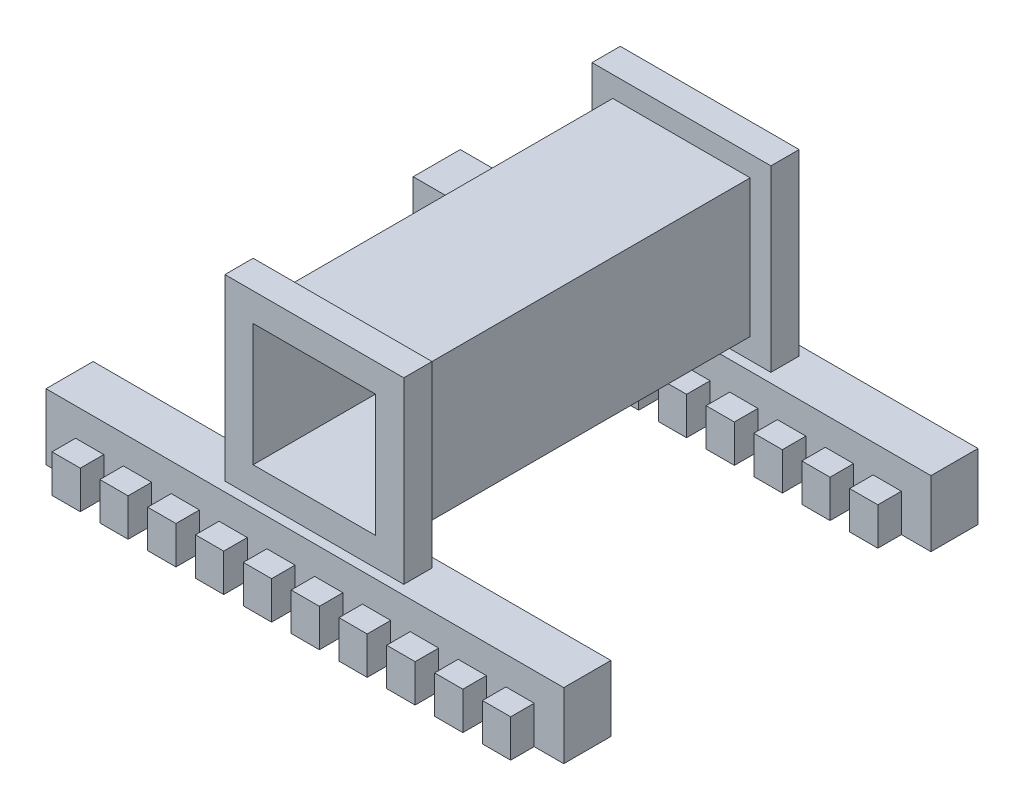
SolidWorks part; units mm, degrees
ref_plane "前视基准面" through (0, 0, 0) normal (0, 0, 1) x (1, 0, 0)
ref_plane "上视基准面" through (0, 0, 0) normal (0, 1, 0) x (1, 0, 0)
ref_plane "右视基准面" through (0, 0, 0) normal (1, 0, 0) x (0, 0, -1)
sketch "草图1" plane through (0, 0, 0) normal (0, 0, 1) x (1, 0, 0)
  line L0 (-9.5, 9.5) -> (9.5, 9.5)
  line L1 (-6.5, -6.5) -> (6.5, -6.5)
  line L2 (-6.5, -6.5) -> (-6.5, 6.5)
  line L3 (-6.5, 6.5) -> (6.5, 6.5)
  line L4 (6.5, -6.5) -> (6.5, 6.5)
  line L5 (-6.5, -6.5) -> (6.5, 6.5) construction
  line L6 (-6.5, 6.5) -> (6.5, -6.5) construction
  line L7 (9.5, -9.5) -> (9.5, 9.5)
  line L8 (-9.5, -9.5) -> (9.5, -9.5)
  line L9 (-9.5, -9.5) -> (-9.5, 9.5)
  line L10 (-7.3, 7.3) -> (7.3, 7.3)
  line L11 (7.3, -7.3) -> (7.3, 7.3)
  line L12 (-7.3, -7.3) -> (7.3, -7.3)
  line L13 (-7.3, -7.3) -> (-7.3, 7.3)
  line L15 (-27.5, -9.5) -> (27.5, -9.5)
  line L16 (-27.5, -9.5) -> (-27.5, -16.5)
  line L17 (-27.5, -16.5) -> (27.5, -16.5)
  line L18 (27.5, -9.5) -> (27.5, -16.5)
  point P0 (0, 0)
  dimension "D1" = 3
  dimension "D2" = 0.8
extrude "凸台-拉伸1" add sketch "草图1" along normal mid plane 42 contours L18 L15 L8 L16 L17 | L9 L8 L7 L0 L12 L13 L10 L11 | L13 L10 L11 L12 region at (0, 9.2313, 0) region at (0, -13, 0)
extrude "切除-拉伸1" cut sketch "草图1<3>" against normal mid plane 42 contours L2 L3 L4 L1
sketch "草图1<3>" plane through (0, 0, 0) normal (0, 0, 1) x (1, 0, 0) same geometry as "草图1"
sketch "草图2" plane through (0, 0, 0) normal (1, 0, 0) x (0, 0, -1)
  line L0 (21, -16.5) -> (21, -9.5) construction
  line L1 (21, -9.5) -> (-21, -9.5) construction
  line L2 (-21, -9.5) -> (-21, -16.5) construction
  line L3 (-21, -16.5) -> (21, -16.5) construction
  line L4 (21, -9.5) -> (21, 9.5) construction
  line L5 (21, 9.5) -> (-21, 9.5) construction
  line L6 (-21, 9.5) -> (-21, -9.5) construction
  line L7 (-21, -9.5) -> (21, -9.5) construction
  line L8 (21, -16.5) -> (21, -9.5)
  line L9 (21, -9.5) -> (-21, -9.5)
  line L10 (-21, -9.5) -> (-21, -16.5)
  line L11 (-21, -16.5) -> (21, -16.5)
  line L12 (21, -9.5) -> (21, 9.5)
  line L13 (21, 9.5) -> (-21, 9.5)
  line L14 (-21, 9.5) -> (-21, -9.5)
  line L15 (-21, -9.5) -> (21, -9.5)
extrude "切除-拉伸6" cut sketch "草图1<12>" against normal mid plane 36 contours L1 L4 L3 L2 | L9 L0 L7 L8 | L13 L10 L11 L12 region at (0, 0, 0)
sketch "草图1<12>" plane through (0, 0, 0) normal (0, 0, 1) x (1, 0, 0) same geometry as "草图1"
extrude "切除-拉伸7" cut sketch "草图1<13>" against normal mid plane 29 contours L18 L15 L8 L16 L17 region at (0, -13, 0)
sketch "草图1<13>" plane through (0, 0, 0) normal (0, 0, 1) x (1, 0, 0) same geometry as "草图1"
sketch "草图4" plane through (0, 0, 0) normal (1, 0, 0) x (0, 0, -1)
  line L0 (-21, -9.5) -> (-14.5, -9.5) construction
  line L1 (-14.5, -9.5) -> (-14.5, -16.5) construction
  line L2 (-14.5, -16.5) -> (-21, -16.5) construction
  line L3 (-21, -16.5) -> (-21, -9.5) construction
  line L4 (-18, 9.5) -> (-18, -9.5) construction
  line L5 (-18, -9.5) -> (-21, -9.5) construction
  line L6 (-21, -9.5) -> (-21, 9.5) construction
  line L7 (-21, 9.5) -> (-18, 9.5) construction
  line L8 (-18, -7.3) -> (-18, 7.3) construction
  line L9 (-18, 7.3) -> (18, 7.3) construction
  line L10 (18, 7.3) -> (18, -7.3) construction
  line L11 (18, -7.3) -> (-18, -7.3) construction
  line L12 (21, -9.5) -> (18, -9.5) construction
  line L13 (18, -9.5) -> (18, 9.5) construction
  line L14 (18, 9.5) -> (21, 9.5) construction
  line L15 (21, 9.5) -> (21, -9.5) construction
  line L16 (14.5, -16.5) -> (14.5, -9.5) construction
  line L17 (14.5, -9.5) -> (21, -9.5) construction
  line L18 (21, -9.5) -> (21, -16.5) construction
  line L19 (21, -16.5) -> (14.5, -16.5) construction
  line L20 (-21, -9.5) -> (-14.5, -9.5)
  line L21 (-14.5, -9.5) -> (-14.5, -16.5)
  line L22 (-14.5, -16.5) -> (-21, -16.5)
  line L23 (-21, -16.5) -> (-21, -9.5)
  line L24 (-18, 9.5) -> (-18, -9.5)
  line L25 (-18, -9.5) -> (-21, -9.5)
  line L26 (-21, -9.5) -> (-21, 9.5)
  line L27 (-21, 9.5) -> (-18, 9.5)
  line L28 (-18, -7.3) -> (-18, 7.3)
  line L29 (-18, 7.3) -> (18, 7.3)
  line L30 (18, 7.3) -> (18, -7.3)
  line L31 (18, -7.3) -> (-18, -7.3)
  line L32 (21, -9.5) -> (18, -9.5)
  line L33 (18, -9.5) -> (18, 9.5)
  line L34 (18, 9.5) -> (21, 9.5)
  line L35 (21, 9.5) -> (21, -9.5)
  line L36 (14.5, -16.5) -> (14.5, -9.5)
  line L37 (14.5, -9.5) -> (21, -9.5)
  line L38 (21, -9.5) -> (21, -16.5)
  line L39 (21, -16.5) -> (14.5, -16.5)
  line L40 (21, -9.5) -> (24.5, -9.5)
  line L41 (24.5, -9.5) -> (24.5, -16.5)
  line L42 (24.5, -16.5) -> (21, -16.5)
  line L43 (-21, -16.5) -> (-24.5049, -16.5)
  line L44 (-24.5049, -16.5) -> (-24.5049, -9.5)
  line L45 (-24.5049, -9.5) -> (-21, -9.5)
extrude "凸台-拉伸2" add sketch "草图4" along normal mid plane 55 contours L42 L41 L40 L38 | L45 L44 L43 L23 region at (0, -13, 22.7525) region at (0, -13, -22.75)
sketch "草图5" plane through (0, 0, -24.5) normal (0, 0, -1) x (-1, 0, 0)
  line L3 (-17.78, -12.5036) -> (-17.78, -16.5)
  line L4 (27.5, -16.5) -> (27.5, -9.5)
  line L5 (27.5, -9.5) -> (-27.5, -9.5)
  line L6 (-27.5, -9.5) -> (-27.5, -16.5)
  line L7 (-27.5, -16.5) -> (27.5, -16.5)
  line L8 (27.5, -16.5) -> (27.5, -9.5)
  line L9 (27.5, -9.5) -> (-27.5, -9.5)
  line L10 (-27.5, -9.5) -> (-27.5, -16.5)
  line L12 (-9.5, -9.5) -> (9.5, -9.5)
  line L13 (-9.5, 9.5) -> (-9.5, -9.5)
  line L14 (9.5, 9.5) -> (-9.5, 9.5)
  line L15 (9.5, -9.5) -> (9.5, 9.5)
  line L16 (-9.5, -9.5) -> (9.5, -9.5)
  line L17 (-9.5, 9.5) -> (-9.5, -9.5)
  line L18 (9.5, 9.5) -> (-9.5, 9.5)
  line L19 (9.5, -9.5) -> (9.5, 9.5)
  line L20 (-17.78, -16.5) -> (-12.7, -16.5)
  line L21 (-12.7, -16.5) -> (-12.7, -12.5036)
  line L23 (-7.62, -12.5036) -> (-7.62, -16.5)
  line L24 (-27.5, -16.5) -> (27.5, -16.5) construction
  line L26 (-2.54, -16.5) -> (-2.54, -12.4956)
  line L30 (7.62, -16.5) -> (7.62, -12.5)
  line L32 (12.7, -12.5) -> (12.7, -16.5)
  line L33 (12.7, -16.5) -> (17.78, -16.5)
  line L34 (17.78, -16.5) -> (17.78, -12.487)
  line L36 (22.8593, -12.487) -> (22.8593, -16.5)
  line L37 (22.8593, -16.5) -> (27.5, -16.5)
  line L38 (-27.5, -16.5) -> (-22.86, -16.5)
  line L49 (-12.7, -12.5036) -> (-7.62, -12.5036)
  line L50 (-21.36, -16.5) -> (-24.36, -16.5)
  line L55 (-11.187, -12.5036) -> (-14.213, -12.5036)
  line L56 (-11.187, -12.5036) -> (-11.187, -16.5)
  line L61 (-6.12, -16.5) -> (-9.12, -16.5)
  line L62 (-6.12, -16.5) -> (-6.12, -12.5036)
  line L67 (-7.62, -16.5) -> (-2.54, -16.5)
  line L68 (-1.04, -16.4978) -> (-4.04, -16.4978)
  line L73 (-2.54, -12.4956) -> (2.539, -12.4956)
  line L74 (2.539, -16.5) -> (7.62, -16.5)
  line L79 (7.62, -12.5) -> (12.7, -12.5)
  line L80 (17.78, -12.487) -> (22.8593, -12.487)
  line L86 (9.12, -16.5) -> (6.12, -16.5)
  line L91 (9.12, -16.5) -> (9.12, -12.5)
  line L92 (9.12, -12.5) -> (6.12, -12.5)
  line L97 (6.12, -16.5) -> (6.12, -12.5)
  line L98 (9.12, -16.5) -> (6.12, -12.5) construction
  line L101 (-22.86, -16.5) -> (-22.86, -12.5036)
  line L102 (-22.86, -12.5036) -> (-17.78, -12.5036)
  line L103 (-21.36, -16.5) -> (-21.36, -12.5036)
  line L104 (-21.36, -12.5036) -> (-24.36, -12.5036)
  line L105 (-24.36, -16.5) -> (-24.36, -12.5036)
  line L106 (-21.36, -16.5) -> (-24.36, -12.5036) construction
  line L107 (-21.36, -12.5036) -> (-24.36, -16.5) construction
  line L108 (-19.28, -16.5) -> (-16.28, -16.5)
  line L109 (-19.28, -16.5) -> (-19.28, -12.5036)
  line L110 (-19.28, -12.5036) -> (-16.28, -12.5036)
  line L111 (-16.28, -16.5) -> (-16.28, -12.5036)
  line L112 (-19.28, -16.5) -> (-16.28, -12.5036) construction
  line L113 (-19.28, -12.5036) -> (-16.28, -16.5) construction
  line L114 (-11.187, -16.5) -> (-14.213, -16.5)
  line L115 (-14.213, -12.5036) -> (-14.213, -16.5)
  line L116 (-11.187, -12.5036) -> (-14.213, -16.5) construction
  line L117 (-11.187, -16.5) -> (-14.213, -12.5036) construction
  line L118 (-6.12, -12.5036) -> (-9.12, -12.5036)
  line L119 (-9.12, -16.5) -> (-9.12, -12.5036)
  line L120 (-6.12, -16.5) -> (-9.12, -12.5036) construction
  line L121 (-6.12, -12.5036) -> (-9.12, -16.5) construction
  line L122 (-1.04, -16.4978) -> (-1.04, -12.4978)
  line L123 (-1.04, -12.4978) -> (-4.04, -12.4978)
  line L124 (-4.04, -16.4978) -> (-4.04, -12.4978)
  line L125 (-1.04, -16.4978) -> (-4.04, -12.4978) construction
  line L126 (-1.04, -12.4978) -> (-4.04, -16.4978) construction
  line L127 (2.539, -12.4956) -> (2.539, -16.5)
  line L128 (9.12, -12.5) -> (6.12, -16.5) construction
  line L129 (4.04, -16.5) -> (1.038, -16.5)
  line L130 (4.04, -16.5) -> (4.04, -12.4956)
  line L131 (4.04, -12.4956) -> (1.038, -12.4956)
  line L132 (1.038, -16.5) -> (1.038, -12.4956)
  line L133 (4.04, -16.5) -> (1.038, -12.4956) construction
  line L134 (4.04, -12.4956) -> (1.038, -16.5) construction
  line L135 (14.2014, -16.5) -> (11.1986, -16.5)
  line L136 (14.2014, -16.5) -> (14.2014, -12.5)
  line L137 (14.2014, -12.5) -> (11.1986, -12.5)
  line L138 (11.1986, -16.5) -> (11.1986, -12.5)
  line L139 (14.2014, -16.5) -> (11.1986, -12.5) construction
  line L140 (14.2014, -12.5) -> (11.1986, -16.5) construction
  line L141 (19.28, -16.4935) -> (16.28, -16.4935)
  line L142 (19.28, -16.4935) -> (19.28, -12.4935)
  line L143 (19.28, -12.4935) -> (16.28, -12.4935)
  line L144 (16.28, -16.4935) -> (16.28, -12.4935)
  line L145 (19.28, -16.4935) -> (16.28, -12.4935) construction
  line L146 (19.28, -12.4935) -> (16.28, -16.4935) construction
  line L151 (24.3586, -16.5) -> (21.36, -16.5)
  line L152 (24.3586, -16.5) -> (24.3586, -12.487)
  line L153 (24.3586, -12.487) -> (21.36, -12.487)
  line L154 (21.36, -16.5) -> (21.36, -12.487)
  line L155 (24.3586, -16.5) -> (21.36, -12.487) construction
  line L156 (24.3586, -12.487) -> (21.36, -16.5) construction
  point P6 (-22.86, -14.5018)
  point P33 (-17.78, -14.5018)
  point P35 (-17.78, -14.5018)
  point P39 (-12.7, -14.5018)
  point P40 (-12.7, -14.5018)
  point P45 (-7.62, -14.5018)
  point P50 (-2.54, -14.4978)
  point P55 (2.539, -14.4978)
  point P60 (7.62, -14.5)
  point P65 (12.7, -14.5)
  point P70 (17.78, -14.4935)
  point P75 (22.8593, -14.4935)
  line M42 (27.5, -16.5) -> (27.5, -9.5)
  line M43 (27.5, -9.5) -> (-27.5, -9.5)
  line M44 (-27.5, -9.5) -> (-27.5, -16.5)
  line M45 (-27.5, -16.5) -> (27.5, -16.5)
  dimension "D1" = 0
  dimension "D2" = 0
extrude "切除-拉伸8" cut sketch "草图5" against normal blind 2.5 contours L153 L152 L37 L9 L105 L104 L102 L110 L111 L20 L115 L55 L49 L118 L62 L26 L68 L124 L123 L73 L131 L130 L74 L97 L92 L79 L137 L136 L33 L34 L141 L144 L143 L80 M42 M43 M44 M45 | L109 L102 L103 M45 | L119 L49 L56 M45 | L132 L73 L26 L123 L122 L68 M45 | L138 L79 L91 M45 | L154 L80 L34 L143 L142 L141 M45 region at (0.0086, -11.9144, -24.5) region at (20.32, -14.5018, -24.5) region at (10.1535, -14.5018, -24.5) region at (0.0024, -14.4978, -24.5) region at (-20.3158, -14.4935, -24.5) region at (-10.1593, -14.5, -24.5)
sketch "草图7" plane through (0, 0, -14.5) normal (0, 0, 1) x (1, 0, 0)
  line L0 (-21.36, -12.487) -> (-21.36, -16.5) construction
  line L1 (-21.36, -16.5) -> (-24.3586, -16.5) construction
  line L2 (-24.3586, -16.5) -> (-24.3586, -12.487) construction
  line L3 (-24.3586, -12.487) -> (-21.36, -12.487) construction
  line L4 (27.5, -16.5) -> (27.5, -9.5)
  line L5 (27.5, -9.5) -> (-27.5, -9.5)
  line L6 (-27.5, -9.5) -> (-27.5, -16.5)
  line L7 (-27.5, -16.5) -> (27.5, -16.5)
  line L8 (27.5, -16.5) -> (27.5, -9.5)
  line L9 (27.5, -9.5) -> (-27.5, -9.5)
  line L10 (-27.5, -9.5) -> (-27.5, -16.5)
  line L11 (-27.5, -16.5) -> (27.5, -16.5)
  line L12 (-16.28, -16.4935) -> (-19.28, -16.4935) construction
  line L13 (-19.28, -16.4935) -> (-19.28, -12.4935) construction
  line L14 (-19.28, -12.4935) -> (-16.28, -12.4935) construction
  line L15 (-16.28, -12.4935) -> (-16.28, -16.4935) construction
  line L16 (-11.1986, -16.5) -> (-14.2014, -16.5) construction
  line L17 (-14.2014, -16.5) -> (-14.2014, -12.5) construction
  line L18 (-14.2014, -12.5) -> (-11.1986, -12.5) construction
  line L19 (-11.1986, -12.5) -> (-11.1986, -16.5) construction
  line L20 (-6.12, -16.5) -> (-9.12, -16.5) construction
  line L21 (-9.12, -16.5) -> (-9.12, -12.5) construction
  line L22 (-9.12, -12.5) -> (-6.12, -12.5) construction
  line L23 (-6.12, -12.5) -> (-6.12, -16.5) construction
  line L24 (-1.038, -16.5) -> (-4.04, -16.5) construction
  line L25 (-4.04, -16.5) -> (-4.04, -12.4956) construction
  line L26 (-4.04, -12.4956) -> (-1.038, -12.4956) construction
  line L27 (-1.038, -12.4956) -> (-1.038, -16.5) construction
  line L28 (4.04, -16.4978) -> (1.04, -16.4978) construction
  line L29 (1.04, -16.4978) -> (1.04, -12.4978) construction
  line L30 (1.04, -12.4978) -> (4.04, -12.4978) construction
  line L31 (4.04, -12.4978) -> (4.04, -16.4978) construction
  line L32 (9.12, -16.5) -> (6.12, -16.5) construction
  line L33 (6.12, -16.5) -> (6.12, -12.5036) construction
  line L34 (6.12, -12.5036) -> (9.12, -12.5036) construction
  line L35 (9.12, -12.5036) -> (9.12, -16.5) construction
  line L36 (11.187, -16.5) -> (11.187, -12.5036) construction
  line L37 (11.187, -12.5036) -> (14.213, -12.5036) construction
  line L38 (14.213, -12.5036) -> (14.213, -16.5) construction
  line L39 (14.213, -16.5) -> (11.187, -16.5) construction
  line L40 (19.28, -16.5) -> (16.28, -16.5) construction
  line L41 (16.28, -16.5) -> (16.28, -12.5036) construction
  line L42 (16.28, -12.5036) -> (19.28, -12.5036) construction
  line L43 (19.28, -12.5036) -> (19.28, -16.5) construction
  line L44 (24.36, -16.5) -> (21.36, -16.5) construction
  line L45 (21.36, -16.5) -> (21.36, -12.5036) construction
  line L46 (21.36, -12.5036) -> (24.36, -12.5036) construction
  line L47 (24.36, -12.5036) -> (24.36, -16.5) construction
  line L48 (-21.36, -12.487) -> (-21.36, -16.5)
  line L49 (-21.36, -16.5) -> (-24.3586, -16.5)
  line L50 (-24.3586, -16.5) -> (-24.3586, -12.487)
  line L51 (-24.3586, -12.487) -> (-21.36, -12.487)
  line L52 (-16.28, -16.4935) -> (-19.28, -16.4935)
  line L53 (-19.28, -16.4935) -> (-19.28, -12.4935)
  line L54 (-19.28, -12.4935) -> (-16.28, -12.4935)
  line L55 (-16.28, -12.4935) -> (-16.28, -16.4935)
  line L56 (-11.1986, -16.5) -> (-14.2014, -16.5)
  line L57 (-14.2014, -16.5) -> (-14.2014, -12.5)
  line L58 (-14.2014, -12.5) -> (-11.1986, -12.5)
  line L59 (-11.1986, -12.5) -> (-11.1986, -16.5)
  line L60 (-6.12, -16.5) -> (-9.12, -16.5)
  line L61 (-9.12, -16.5) -> (-9.12, -12.5)
  line L62 (-9.12, -12.5) -> (-6.12, -12.5)
  line L63 (-6.12, -12.5) -> (-6.12, -16.5)
  line L64 (-1.038, -16.5) -> (-4.04, -16.5)
  line L65 (-4.04, -16.5) -> (-4.04, -12.4956)
  line L66 (-4.04, -12.4956) -> (-1.038, -12.4956)
  line L67 (-1.038, -12.4956) -> (-1.038, -16.5)
  line L68 (4.04, -16.4978) -> (1.04, -16.4978)
  line L69 (1.04, -16.4978) -> (1.04, -12.4978)
  line L70 (1.04, -12.4978) -> (4.04, -12.4978)
  line L71 (4.04, -12.4978) -> (4.04, -16.4978)
  line L72 (9.12, -16.5) -> (6.12, -16.5)
  line L73 (6.12, -16.5) -> (6.12, -12.5036)
  line L74 (6.12, -12.5036) -> (9.12, -12.5036)
  line L75 (9.12, -12.5036) -> (9.12, -16.5)
  line L76 (11.187, -16.5) -> (11.187, -12.5036)
  line L77 (11.187, -12.5036) -> (14.213, -12.5036)
  line L78 (14.213, -12.5036) -> (14.213, -16.5)
  line L79 (14.213, -16.5) -> (11.187, -16.5)
  line L80 (19.28, -16.5) -> (16.28, -16.5)
  line L81 (16.28, -16.5) -> (16.28, -12.5036)
  line L82 (16.28, -12.5036) -> (19.28, -12.5036)
  line L83 (19.28, -12.5036) -> (19.28, -16.5)
  line L84 (24.36, -16.5) -> (21.36, -16.5)
  line L85 (21.36, -16.5) -> (21.36, -12.5036)
  line L86 (21.36, -12.5036) -> (24.36, -12.5036)
  line L87 (24.36, -12.5036) -> (24.36, -16.5)
  line M5 (27.5, -16.5) -> (27.5, -9.5)
  line M6 (27.5, -9.5) -> (-27.5, -9.5)
  line M7 (-27.5, -9.5) -> (-27.5, -16.5)
  line M8 (-27.5, -16.5) -> (27.5, -16.5)
  dimension "D1" = 0
extrude "切除-拉伸9" cut sketch "草图7" against normal blind 2.5 contours L86 L87 L11 L50 L51 L48 L57 L58 L59 L61 L62 L63 L65 L66 L67 L73 L74 L75 L76 L77 L78 L81 L82 L83 L85 L54 L55 L52 L53 L70 L71 L68 L69 M5 M6 M7 M8 region at (0.0011, -12.3202, -14.5)
sketch "草图9" plane through (0, 0, 14.5) normal (0, 0, -1) x (-1, 0, 0)
  line L0 (-24.36, -16.5) -> (-21.36, -16.5) construction
  line L1 (-21.36, -16.5) -> (-21.36, -12.5036) construction
  line L2 (-21.36, -12.5036) -> (-24.36, -12.5036) construction
  line L3 (-24.36, -12.5036) -> (-24.36, -16.5) construction
  line L4 (-27.5, -9.5) -> (-27.5, -16.5)
  line L5 (-27.5, -16.5) -> (27.5, -16.5)
  line L6 (27.5, -16.5) -> (27.5, -9.5)
  line L7 (27.5, -9.5) -> (-27.5, -9.5)
  line L8 (-27.5, -9.5) -> (-27.5, -16.5)
  line L9 (-27.5, -16.5) -> (27.5, -16.5)
  line L10 (27.5, -16.5) -> (27.5, -9.5)
  line L11 (27.5, -9.5) -> (-27.5, -9.5)
  line L12 (-19.28, -16.5) -> (-16.28, -16.5) construction
  line L13 (-16.28, -16.5) -> (-16.28, -12.5036) construction
  line L14 (-16.28, -12.5036) -> (-19.28, -12.5036) construction
  line L15 (-19.28, -12.5036) -> (-19.28, -16.5) construction
  line L16 (-11.187, -16.5) -> (-11.187, -12.5036) construction
  line L17 (-11.187, -12.5036) -> (-14.213, -12.5036) construction
  line L18 (-14.213, -12.5036) -> (-14.213, -16.5) construction
  line L19 (-14.213, -16.5) -> (-11.187, -16.5) construction
  line L20 (-9.12, -16.5) -> (-6.12, -16.5) construction
  line L21 (-6.12, -16.5) -> (-6.12, -12.5036) construction
  line L22 (-6.12, -12.5036) -> (-9.12, -12.5036) construction
  line L23 (-9.12, -12.5036) -> (-9.12, -16.5) construction
  line L24 (-4.04, -16.4978) -> (-1.04, -16.4978) construction
  line L25 (-1.04, -16.4978) -> (-1.04, -12.4978) construction
  line L26 (-1.04, -12.4978) -> (-4.04, -12.4978) construction
  line L27 (-4.04, -12.4978) -> (-4.04, -16.4978) construction
  line L28 (1.038, -16.5) -> (4.04, -16.5) construction
  line L29 (4.04, -16.5) -> (4.04, -12.4956) construction
  line L30 (4.04, -12.4956) -> (1.038, -12.4956) construction
  line L31 (1.038, -12.4956) -> (1.038, -16.5) construction
  line L32 (6.12, -16.5) -> (9.12, -16.5) construction
  line L33 (9.12, -16.5) -> (9.12, -12.5) construction
  line L34 (9.12, -12.5) -> (6.12, -12.5) construction
  line L35 (6.12, -12.5) -> (6.12, -16.5) construction
  line L36 (11.1986, -16.5) -> (14.2014, -16.5) construction
  line L37 (14.2014, -16.5) -> (14.2014, -12.5) construction
  line L38 (14.2014, -12.5) -> (11.1986, -12.5) construction
  line L39 (11.1986, -12.5) -> (11.1986, -16.5) construction
  line L40 (16.28, -16.4935) -> (19.28, -16.4935) construction
  line L41 (19.28, -16.4935) -> (19.28, -12.4935) construction
  line L42 (19.28, -12.4935) -> (16.28, -12.4935) construction
  line L43 (16.28, -12.4935) -> (16.28, -16.4935) construction
  line L44 (21.36, -12.487) -> (21.36, -16.5) construction
  line L45 (21.36, -16.5) -> (24.3586, -16.5) construction
  line L46 (24.3586, -16.5) -> (24.3586, -12.487) construction
  line L47 (24.3586, -12.487) -> (21.36, -12.487) construction
  line L48 (-24.36, -16.5) -> (-21.36, -16.5)
  line L49 (-21.36, -16.5) -> (-21.36, -12.5036)
  line L50 (-21.36, -12.5036) -> (-24.36, -12.5036)
  line L51 (-24.36, -12.5036) -> (-24.36, -16.5)
  line L52 (-19.28, -16.5) -> (-16.28, -16.5)
  line L53 (-16.28, -16.5) -> (-16.28, -12.5036)
  line L54 (-16.28, -12.5036) -> (-19.28, -12.5036)
  line L55 (-19.28, -12.5036) -> (-19.28, -16.5)
  line L56 (-11.187, -16.5) -> (-11.187, -12.5036)
  line L57 (-11.187, -12.5036) -> (-14.213, -12.5036)
  line L58 (-14.213, -12.5036) -> (-14.213, -16.5)
  line L59 (-14.213, -16.5) -> (-11.187, -16.5)
  line L60 (-9.12, -16.5) -> (-6.12, -16.5)
  line L61 (-6.12, -16.5) -> (-6.12, -12.5036)
  line L62 (-6.12, -12.5036) -> (-9.12, -12.5036)
  line L63 (-9.12, -12.5036) -> (-9.12, -16.5)
  line L64 (-4.04, -16.4978) -> (-1.04, -16.4978)
  line L65 (-1.04, -16.4978) -> (-1.04, -12.4978)
  line L66 (-1.04, -12.4978) -> (-4.04, -12.4978)
  line L67 (-4.04, -12.4978) -> (-4.04, -16.4978)
  line L68 (1.038, -16.5) -> (4.04, -16.5)
  line L69 (4.04, -16.5) -> (4.04, -12.4956)
  line L70 (4.04, -12.4956) -> (1.038, -12.4956)
  line L71 (1.038, -12.4956) -> (1.038, -16.5)
  line L72 (6.12, -16.5) -> (9.12, -16.5)
  line L73 (9.12, -16.5) -> (9.12, -12.5)
  line L74 (9.12, -12.5) -> (6.12, -12.5)
  line L75 (6.12, -12.5) -> (6.12, -16.5)
  line L76 (11.1986, -16.5) -> (14.2014, -16.5)
  line L77 (14.2014, -16.5) -> (14.2014, -12.5)
  line L78 (14.2014, -12.5) -> (11.1986, -12.5)
  line L79 (11.1986, -12.5) -> (11.1986, -16.5)
  line L80 (16.28, -16.4935) -> (19.28, -16.4935)
  line L81 (19.28, -16.4935) -> (19.28, -12.4935)
  line L82 (19.28, -12.4935) -> (16.28, -12.4935)
  line L83 (16.28, -12.4935) -> (16.28, -16.4935)
  line L84 (21.36, -12.487) -> (21.36, -16.5)
  line L85 (21.36, -16.5) -> (24.3586, -16.5)
  line L86 (24.3586, -16.5) -> (24.3586, -12.487)
  line L87 (24.3586, -12.487) -> (21.36, -12.487)
  line M5 (-27.5, -9.5) -> (-27.5, -16.5)
  line M6 (-27.5, -16.5) -> (27.5, -16.5)
  line M7 (27.5, -16.5) -> (27.5, -9.5)
  line M8 (27.5, -9.5) -> (-27.5, -9.5)
  dimension "D1" = 0
extrude "切除-拉伸10" cut sketch "草图9" against normal blind 2.5 contours L87 L86 L9 L51 L50 L49 L55 L54 L53 L58 L57 L56 L63 L62 L61 L71 L70 L69 L75 L74 L73 L79 L78 L77 L84 L83 L82 L81 L80 L67 L66 L65 L64 M7 M8 M5 M6 region at (0.0011, -12.3202, 14.5)
sketch "草图10" plane through (0, 0, 24.5049) normal (0, 0, 1) x (1, 0, 0)
  line L0 (21.36, -12.5036) -> (21.36, -16.5) construction
  line L1 (21.36, -16.5) -> (24.36, -16.5) construction
  line L2 (24.36, -16.5) -> (24.36, -12.5036) construction
  line L3 (24.36, -12.5036) -> (21.36, -12.5036) construction
  line L4 (-27.5, -9.5) -> (-27.5, -16.5)
  line L5 (-27.5, -16.5) -> (27.5, -16.5)
  line L6 (27.5, -16.5) -> (27.5, -9.5)
  line L7 (27.5, -9.5) -> (-27.5, -9.5)
  line L8 (-27.5, -9.5) -> (-27.5, -16.5)
  line L9 (-27.5, -16.5) -> (27.5, -16.5)
  line L10 (27.5, -16.5) -> (27.5, -9.5)
  line L11 (27.5, -9.5) -> (-27.5, -9.5)
  line L12 (19.28, -16.5) -> (19.28, -12.5036) construction
  line L13 (19.28, -12.5036) -> (16.28, -12.5036) construction
  line L14 (16.28, -12.5036) -> (16.28, -16.5) construction
  line L15 (16.28, -16.5) -> (19.28, -16.5) construction
  line L16 (14.213, -16.5) -> (14.213, -12.5036) construction
  line L17 (14.213, -12.5036) -> (11.187, -12.5036) construction
  line L18 (11.187, -12.5036) -> (11.187, -16.5) construction
  line L19 (11.187, -16.5) -> (14.213, -16.5) construction
  line L20 (9.12, -16.5) -> (9.12, -12.5036) construction
  line L21 (9.12, -12.5036) -> (6.12, -12.5036) construction
  line L22 (6.12, -12.5036) -> (6.12, -16.5) construction
  line L23 (6.12, -16.5) -> (9.12, -16.5) construction
  line L24 (4.04, -12.4978) -> (1.04, -12.4978) construction
  line L25 (1.04, -12.4978) -> (1.04, -16.4978) construction
  line L26 (1.04, -16.4978) -> (4.04, -16.4978) construction
  line L27 (4.04, -16.4978) -> (4.04, -12.4978) construction
  line L28 (-1.038, -16.5) -> (-1.038, -12.4956) construction
  line L29 (-1.038, -12.4956) -> (-4.04, -12.4956) construction
  line L30 (-4.04, -12.4956) -> (-4.04, -16.5) construction
  line L31 (-4.04, -16.5) -> (-1.038, -16.5) construction
  line L32 (-6.12, -16.5) -> (-6.12, -12.5) construction
  line L33 (-6.12, -12.5) -> (-9.12, -12.5) construction
  line L34 (-9.12, -12.5) -> (-9.12, -16.5) construction
  line L35 (-9.12, -16.5) -> (-6.12, -16.5) construction
  line L36 (-11.1986, -16.5) -> (-11.1986, -12.5) construction
  line L37 (-11.1986, -12.5) -> (-14.2014, -12.5) construction
  line L38 (-14.2014, -12.5) -> (-14.2014, -16.5) construction
  line L39 (-14.2014, -16.5) -> (-11.1986, -16.5) construction
  line L40 (-16.28, -12.4935) -> (-19.28, -12.4935) construction
  line L41 (-19.28, -12.4935) -> (-19.28, -16.4935) construction
  line L42 (-19.28, -16.4935) -> (-16.28, -16.4935) construction
  line L43 (-16.28, -16.4935) -> (-16.28, -12.4935) construction
  line L44 (-21.36, -16.5) -> (-21.36, -12.487) construction
  line L45 (-21.36, -12.487) -> (-24.3586, -12.487) construction
  line L46 (-24.3586, -12.487) -> (-24.3586, -16.5) construction
  line L47 (-24.3586, -16.5) -> (-21.36, -16.5) construction
  line L48 (21.36, -12.5036) -> (21.36, -16.5)
  line L49 (21.36, -16.5) -> (24.36, -16.5)
  line L50 (24.36, -16.5) -> (24.36, -12.5036)
  line L51 (24.36, -12.5036) -> (21.36, -12.5036)
  line L52 (19.28, -16.5) -> (19.28, -12.5036)
  line L53 (19.28, -12.5036) -> (16.28, -12.5036)
  line L54 (16.28, -12.5036) -> (16.28, -16.5)
  line L55 (16.28, -16.5) -> (19.28, -16.5)
  line L56 (14.213, -16.5) -> (14.213, -12.5036)
  line L57 (14.213, -12.5036) -> (11.187, -12.5036)
  line L58 (11.187, -12.5036) -> (11.187, -16.5)
  line L59 (11.187, -16.5) -> (14.213, -16.5)
  line L60 (9.12, -16.5) -> (9.12, -12.5036)
  line L61 (9.12, -12.5036) -> (6.12, -12.5036)
  line L62 (6.12, -12.5036) -> (6.12, -16.5)
  line L63 (6.12, -16.5) -> (9.12, -16.5)
  line L64 (4.04, -12.4978) -> (1.04, -12.4978)
  line L65 (1.04, -12.4978) -> (1.04, -16.4978)
  line L66 (1.04, -16.4978) -> (4.04, -16.4978)
  line L67 (4.04, -16.4978) -> (4.04, -12.4978)
  line L68 (-1.038, -16.5) -> (-1.038, -12.4956)
  line L69 (-1.038, -12.4956) -> (-4.04, -12.4956)
  line L70 (-4.04, -12.4956) -> (-4.04, -16.5)
  line L71 (-4.04, -16.5) -> (-1.038, -16.5)
  line L72 (-6.12, -16.5) -> (-6.12, -12.5)
  line L73 (-6.12, -12.5) -> (-9.12, -12.5)
  line L74 (-9.12, -12.5) -> (-9.12, -16.5)
  line L75 (-9.12, -16.5) -> (-6.12, -16.5)
  line L76 (-11.1986, -16.5) -> (-11.1986, -12.5)
  line L77 (-11.1986, -12.5) -> (-14.2014, -12.5)
  line L78 (-14.2014, -12.5) -> (-14.2014, -16.5)
  line L79 (-14.2014, -16.5) -> (-11.1986, -16.5)
  line L80 (-16.28, -12.4935) -> (-19.28, -12.4935)
  line L81 (-19.28, -12.4935) -> (-19.28, -16.4935)
  line L82 (-19.28, -16.4935) -> (-16.28, -16.4935)
  line L83 (-16.28, -16.4935) -> (-16.28, -12.4935)
  line L84 (-21.36, -16.5) -> (-21.36, -12.487)
  line L85 (-21.36, -12.487) -> (-24.3586, -12.487)
  line L86 (-24.3586, -12.487) -> (-24.3586, -16.5)
  line L87 (-24.3586, -16.5) -> (-21.36, -16.5)
  line M5 (-27.5, -9.5) -> (-27.5, -16.5)
  line M6 (-27.5, -16.5) -> (27.5, -16.5)
  line M7 (27.5, -16.5) -> (27.5, -9.5)
  line M8 (27.5, -9.5) -> (-27.5, -9.5)
  dimension "D1" = 0
extrude "切除-拉伸11" cut sketch "草图10" against normal blind 2.5 contours L86 L85 L84 L9 L78 L77 L76 L74 L73 L72 L70 L69 L68 L62 L61 L60 L58 L57 L56 L54 L53 L52 L48 L51 L50 L83 L82 L81 L80 L67 L66 L65 L64 M6 M7 M8 M5 region at (0.0011, -12.3202, 24.5049)
